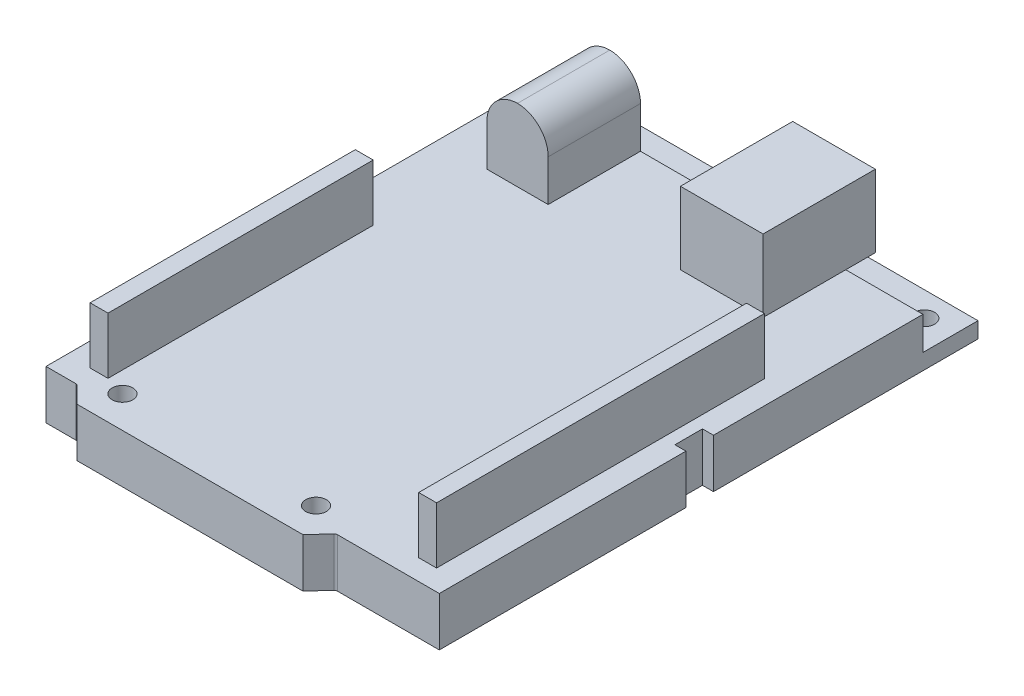
SolidWorks part; units mm, degrees
ref_plane "前视基准面" through (0, 0, 0) normal (0, 0, 1) x (1, 0, 0)
ref_plane "上视基准面" through (0, 0, 0) normal (0, 1, 0) x (1, 0, 0)
ref_plane "右视基准面" through (0, 0, 0) normal (1, 0, 0) x (0, 0, -1)
sketch "草图1" plane through (0, 0, 0) normal (0, 1, 0) x (1, 0, 0)
  line L1 (0, 0) -> (57.1, 0)
  line L2 (0, 0) -> (0, 80.7)
  line L3 (0, 80.7) -> (57.1, 80.7)
  line L4 (57.1, 0) -> (57.1, 80.7)
  dimension "D1" = 57.1
  dimension "D2" = 80.7
extrude "凸台-拉伸1" add sketch "草图1" along normal blind 7.1
sketch "草图3" plane through (0, 7.1, 0) normal (0, 1, 0) x (1, 0, 0)
  line L0 (0, 80.7) -> (0, 72.7)
  line L1 (0, 80.7) -> (0, 0) construction
  line L2 (0, 72.7) -> (57.1, 72.7)
  line L3 (57.1, 0) -> (57.1, 80.7) construction
  line L4 (57.1, 72.7) -> (57.1, 80.7)
  line L5 (57.1, 80.7) -> (0, 80.7)
  dimension "D1" = 8
extrude "切除-拉伸2" cut sketch "草图3" against normal blind 4.8
sketch "草图4" plane through (0, 7.1, 0) normal (0, 1, 0) x (1, 0, 0)
  line L0 (57.1, 0) -> (57.1, 2.5)
  line L1 (57.1, 0) -> (57.1, 72.7) construction
  line L2 (57.1, 2.5) -> (42.3194, 2.5)
  line L3 (41.9514, 2.3385) -> (39.8, 0)
  line L4 (0, 0) -> (57.1, 0) construction
  line L5 (39.8, 0) -> (57.1, 0)
  line L6 (0, 2.5) -> (4.2929, 2.5)
  line L7 (0, 72.7) -> (0, 0) construction
  line L8 (4.6464, 2.3536) -> (7, 0)
  line L9 (7, 0) -> (0, 0)
  line L10 (0, 0) -> (0, 2.5)
  arc A0 (4.2929, 2.5) -> (4.6464, 2.3536) centre (4.2929, 2) cw
  arc A1 (42.3194, 2.5) -> (41.9514, 2.3385) centre (42.3194, 2) ccw
  point P14 (40.0987, 0)
  point P19 (4.5, 2.5)
  point P22 (42.1, 2.5)
  dimension "D6" = 0.5
  dimension "D1" = 2.5
  dimension "D2" = 15
  dimension "D3" = 17.3
  dimension "D4" = 4.5
  dimension "D5" = 7
extrude "切除-拉伸3" cut sketch "草图4" against normal through all
sketch "草图5" plane through (0, 7.1, 0) normal (0, 1, 0) x (1, 0, 0)
  line L0 (57.1, 38.3) -> (55.5, 38.3)
  line L1 (57.1, 2.5) -> (57.1, 72.7) construction
  line L2 (55.5, 38.3) -> (55.5, 42.3)
  line L3 (55.5, 42.3) -> (57.1, 42.3)
  line L4 (57.1, 42.3) -> (57.1, 38.3)
  line L5 (57.1, 2.5) -> (42.3194, 2.5) construction
  dimension "D1" = 1.6
  dimension "D2" = 4
  dimension "D3" = 35.8
extrude "切除-拉伸4" cut sketch "草图5" against normal through all
sketch "草图6" plane through (0, 7.1, 0) normal (0, 1, 0) x (1, 0, 0)
  line L0 (0, 38.3) -> (-1.6, 38.3)
  line L1 (0, 72.7) -> (0, 2.5) construction
  line L2 (-1.6, 38.3) -> (-1.6, 42.3)
  line L3 (-1.6, 42.3) -> (0, 42.3)
  line L4 (0, 42.3) -> (0, 38.3)
  line L5 (57.1, 42.3) -> (55.5, 42.3) construction
  line L6 (55.5, 38.3) -> (57.1, 38.3) construction
  dimension "D1" = 4
  dimension "D2" = 1.6
extrude "凸台-拉伸2" add sketch "草图6" against normal blind 7.1
sketch "草图7" plane through (0, 7.1, 0) normal (0, 1, 0) x (1, 0, 0)
  line L0 (53.7, 5.5) -> (51.1, 5.5)
  line L1 (51.1, 5.5) -> (51.1, 53.1)
  line L2 (51.1, 53.1) -> (53.7, 53.1)
  line L3 (53.7, 53.1) -> (53.7, 5.5)
  line L4 (57.1, 2.5) -> (57.1, 38.3) construction
  line L5 (57.1, 2.5) -> (42.3194, 2.5) construction
  line L6 (6, 5.5) -> (6, 44)
  line L7 (6, 44) -> (3.4, 44)
  line L8 (3.4, 44) -> (3.4, 5.5)
  line L9 (3.4, 5.5) -> (6, 5.5)
  line L10 (0, 38.3) -> (0, 2.5) construction
  dimension "D1" = 2.6
  dimension "D2" = 6
  dimension "D3" = 47.6
  dimension "D4" = 50.6
  dimension "D5" = 2.6
  dimension "D6" = 38.5
  dimension "D7" = 6
extrude "凸台-拉伸3" add sketch "草图7" along normal blind 8.2
sketch "草图8" plane through (0, 7.1, 0) normal (0, 1, 0) x (1, 0, 0)
  line L0 (45.9, 60.7) -> (33.9, 60.7)
  line L1 (33.9, 60.7) -> (33.9, 77)
  line L2 (33.9, 77) -> (45.9, 77)
  line L3 (45.9, 77) -> (45.9, 60.7)
  line L4 (57.1, 42.3) -> (57.1, 72.7) construction
  line L5 (57.1, 80.7) -> (0, 80.7) construction
  dimension "D1" = 12
  dimension "D2" = 16.3
  dimension "D3" = 23.2
  dimension "D4" = 20
extrude "凸台-拉伸4" add sketch "草图8" along normal blind 10.5
sketch "草图9" plane through (0, 7.1, 0) normal (0, 1, 0) x (1, 0, 0)
  line L0 (7.2, 72.7) -> (16.1, 72.7)
  line L1 (0, 72.7) -> (33.9, 72.7) construction
  line L2 (16.1, 72.7) -> (16.1, 69.7)
  line L3 (16.1, 69.7) -> (7.2, 69.7)
  line L4 (7.2, 69.7) -> (7.2, 72.7)
  line L5 (11.65, 69.7) -> (11.65, 88.141) construction
  line L6 (7.2, 69.7) -> (7.2, 59.3)
  line L7 (7.2, 59.3) -> (16.1, 59.3)
  line L8 (16.1, 59.3) -> (16.1, 69.7)
  line L9 (0, 72.7) -> (0, 42.3) construction
  line M20 (33.9, 72.7) -> (0, 72.7)
  dimension "D1" = 8.9
  dimension "D2" = 16.1
  dimension "D3" = 3
  dimension "D4" = 13.4
  dimension "D5" = 8.9
extrude "凸台-拉伸5" add sketch "草图9" along normal blind 10.5 contours L5 L3 L2 M20 | L3 L5 L0 L4 region at (9.425, 7.1, -71.2) region at (13.875, 7.1, -71.2)
sketch "草图10" plane through (0, 7.1, 0) normal (0, 1, 0) x (1, 0, 0)
  line L0 (7.2, 69.7) -> (7.2, 59.3)
  line L1 (7.2, 59.3) -> (16.1, 59.3)
  line L2 (16.1, 59.3) -> (16.1, 69.7)
  line L3 (16.1, 69.7) -> (7.2, 69.7) construction
  line L4 (16.1, 69.7) -> (7.2, 69.7) construction
  line L5 (0, 72.7) -> (7.2, 72.7) construction
  line L6 (7.2, 69.7) -> (16.1, 69.7)
  dimension "D1" = 13.4
extrude "凸台-拉伸6" add sketch "草图10" along normal blind 10.5
fillet "圆角1" radius 4.5 2 edges at (7.2, 17.6, -66) (16.1, 17.6, -66)
sketch "草图11" plane through (0, 2.3, 0) normal (0, 1, 0) x (1, 0, 0)
  line L0 (57.1, 72.7) -> (57.1, 80.7) construction
  line L1 (0, 80.7) -> (0, 72.7) construction
  line L2 (57.1, 80.7) -> (0, 80.7) construction
  line L3 (57.1, 2.5) -> (57.1, 38.3) construction
  line L5 (7, 0) -> (39.8, 0) construction
  line L6 (0, 38.3) -> (0, 2.5) construction
  circle A0 centre (52.9, 77.1) radius 1.5
  circle A1 centre (4.2, 77.1) radius 1.5
  circle A2 centre (37.1, 4.6) radius 1.5
  circle A3 centre (9, 4.6) radius 1.5
  point P18 (36.0462, 1.5745)
  point P19 (34.4357, 0)
  point P22 (0, 0)
  dimension "D1" = 3
  dimension "D6" = 3
  dimension "D2" = 4.2
  dimension "D3" = 4.2
  dimension "D4" = 3.6
  dimension "D5" = 3.6
  dimension "D7" = 20
  dimension "D8" = 4.6
  dimension "D9" = 9
extrude "切除-拉伸7" cut sketch "草图11" against normal through all and the other way through all
